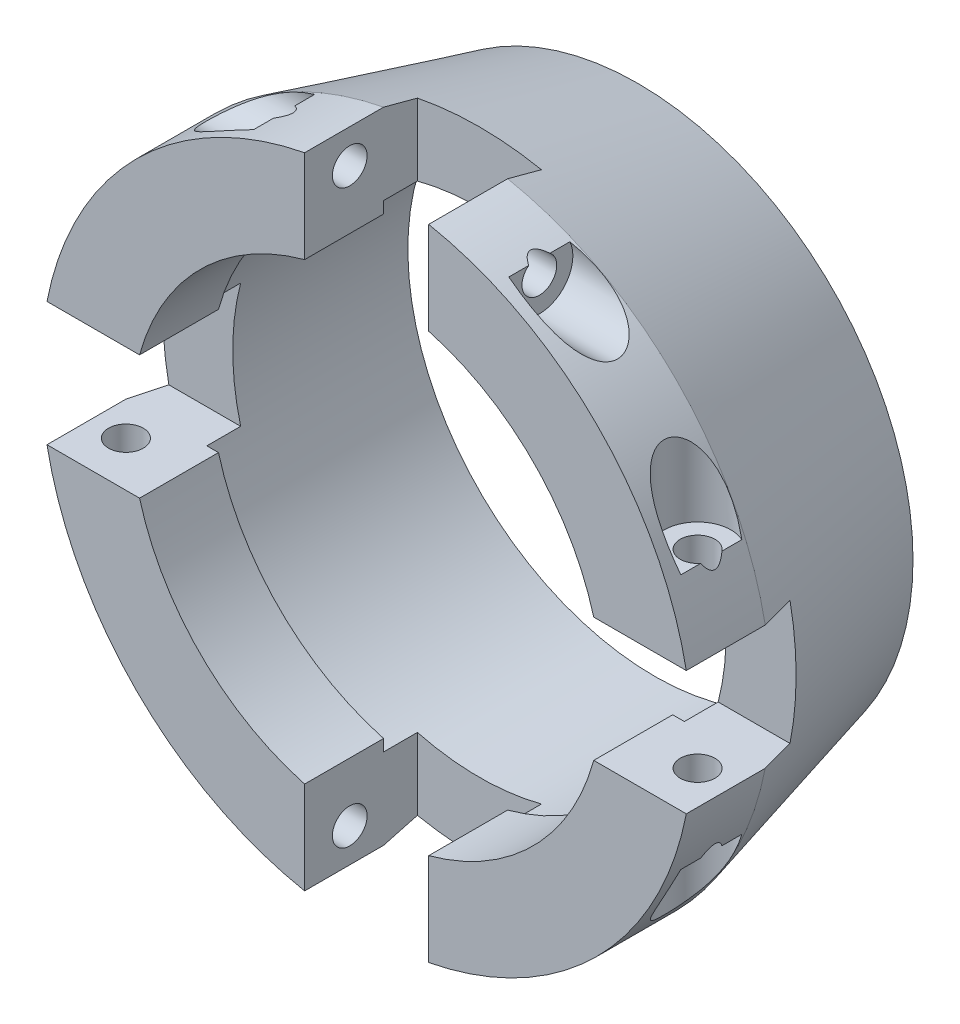
SolidWorks part; units mm, degrees
ref_plane "Front Plane" through (0, 0, 0) normal (1, 0, 0) x (0, 1, 0)
ref_plane "Top Plane" through (0, 0, 0) normal (0, 0, 1) x (0, 1, 0)
ref_plane "Right Plane" through (0, 0, 0) normal (0, 1, 0) x (-1, 0, 0)
sketch "Sketch1" plane through (0, 0, 0) normal (1, 0, 0) x (0, 1, 0)
  line L0 (0, 0) -> (27.7812, 0) construction
  line L1 (0, 0) -> (0, 33.02) construction
  line L2 (27.7812, 0) -> (27.7812, 24.13)
  line L3 (27.7812, 24.13) -> (26.5113, 24.13)
  line L4 (26.5113, 24.13) -> (26.5113, 33.02)
  line L8 (0, 33.02) -> (26.5113, 33.02) construction
  line L11 (27.7812, 0) -> (30.3213, 0)
  line L13 (36.6713, 33.02) -> (26.5113, 33.02)
  line L15 (36.6713, 33.02) -> (36.6713, 24.13)
  line L16 (36.6713, 24.13) -> (30.3213, 0)
  line L17 (27.7812, 24.13) -> (36.6713, 24.13) construction
  point P2 (35.4012, 24.13)
  point P7 (33.105, 0)
  dimension "D1" = 27.7812
  dimension "D2" = 24.13
  dimension "D3" = 8.89
  dimension "D4" = 1.27
  dimension "D5" = 10.16
  dimension "D6" = 2.54
revolve "base_ring" add sketch "Sketch1" angle 360 about L1
sketch "Sketch5" plane through (0, 0, 33.02) normal (0, 0, 1) x (1, 0, 0)
  line L0 (0, 0) -> (0, 25.5745) construction
  line L1 (-6.985, 38.2745) -> (6.985, 38.2745)
  line L2 (-6.985, 38.2745) -> (-6.985, 25.5745)
  line L3 (-6.985, 25.5745) -> (6.985, 25.5745)
  line L4 (6.985, 38.2745) -> (6.985, 25.5745)
  circle A0 centre (0, 0) radius 26.5113 construction
  dimension "D1" = 13.97
  dimension "D2" = 12.7
extrude "pulley_recess" cut sketch "Sketch5" against normal blind 12.7 and the other way through all
ref_plane "Plane1" through (36.6713, 0, 0) normal (1, 0, 0) x (0, 0, -1)
sketch "Sketch7" plane through (36.6713, 0, 0) normal (1, 0, 0) x (0, 0, -1)
  line L6 (-27.94, 32.1899) -> (-27.94, 35.9999) construction
  line L7 (-24.13, 35.9999) -> (-33.02, 35.9999) construction
  line L9 (-24.13, 35.9999) -> (-24.13, -36.6713) construction
  point P0 (-27.94, 32.1899)
  dimension "D1" = 3.81
  dimension "D2" = 3.81
hole_wizard "pulley_bolt_hole" positions "Sketch7" profile "Sketch8" counterbore size "#5" standard "ANSI Inch"
sketch "Sketch8" plane through (36.6713, 32.1899, 27.94) normal (0, 1, 0) x (0, 0, -1)
  line L0 (0, 0) -> (0, 39.2752)
  line L1 (0, 39.2752) -> (1.9558, 38.1)
  line L2 (1.9558, 38.1) -> (1.9558, 22.3012)
  line L3 (1.9558, 22.3012) -> (3.7706, 22.3012)
  line L4 (3.7706, 22.3012) -> (3.7706, 0)
  line L5 (3.7706, 0) -> (0, 0)
  line L10 (0, 39.2752) -> (-1.9558, 38.1) construction
  line L11 (0, -6.35) -> (0, 107.95) construction
  dimension "Hole Dia." = 3.9116
  dimension "Hole Depth" = 38.1
  dimension "C'Bore Dia." = 7.5413
  dimension "C'Bore Depth" = 22.3012
  dimension "Drill Angle" = 118
mirror "bolthole_mirror" about plane through (0, 0, 0) normal (1, 0, 0) of "pulley_bolt_hole"
pattern_circular "CirPattern1" count 4 over 360 about axis through (0, 0, 0) along (0, 0, -1) of "pulley_recess", "pulley_bolt_hole", "bolthole_mirror"
chamfer "Chamfer1" distance 2.54 angle 45 1 edges at (-30.3213, 0, 0) first distance on face at (-30.3213, 0, 0)
